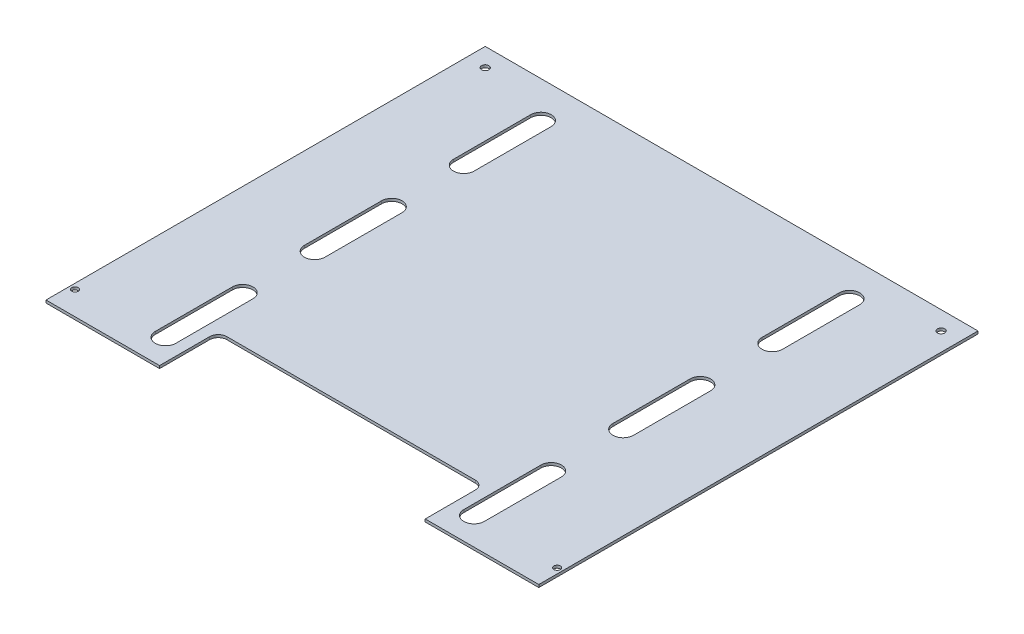
SolidWorks part; units mm, degrees
material "PC High Viscosity"
ref_plane "Front Plane" through (0, 0, 0) normal (0, 0, 1) x (1, 0, 0)
ref_plane "Top Plane" through (0, 0, 0) normal (0, 1, 0) x (1, 0, 0)
ref_plane "Right Plane" through (0, 0, 0) normal (1, 0, 0) x (0, 0, -1)
sketch "Sketch1" plane through (0, 0, 0) normal (0, 1, 0) x (1, 0, 0)
  line L1 (-146.05, 130.175) -> (146.05, 130.175)
  line L2 (-146.05, 130.175) -> (-146.05, -130.175)
  line L3 (-146.05, -130.175) -> (146.05, -130.175)
  line L4 (146.05, 130.175) -> (146.05, -130.175)
  line L5 (-146.05, 130.175) -> (146.05, -130.175) construction
  line L6 (-146.05, -130.175) -> (146.05, 130.175) construction
  line L16 (-135.128, 119.253) -> (135.128, 119.253) construction
  line L18 (-91.44, 18.923) -> (-91.44, -25.273) construction
  line L19 (91.44, 18.923) -> (91.44, -25.273) construction
  line L20 (-91.44, -3.175) -> (91.44, -3.175) construction
  line L21 (0, 127) -> (0, -88.9) construction
  circle A4 centre (-135.128, 119.253) radius 2.1527
  circle A6 centre (135.128, 119.253) radius 2.1527
  point P0 (0, 0)
  point P6 (0, 0)
  point P7 (0, 0)
  point P13 (0, -88.9)
  point P14 (0, -130.175)
  point P37 (0, 119.253)
  dimension "D9" = 4.3053
  dimension "D1" = 292.1
  dimension "D2" = 260.35
  dimension "D7" = 10.922
  dimension "D8" = 10.922
extrude "Boss-Extrude1" add sketch "Sketch1" along normal blind 1.5875 contours L1 L2 L3 L4 region at (0, 0, 0.0457)
sketch "Sketch5" plane through (0, 1.5875, 0) normal (0, 1, 0) x (1, 0, 0)
  line L0 (-91.44, 108.585) -> (-91.44, 62.865) construction
  line L1 (-85.344, 108.585) -> (-85.344, 62.865)
  line L2 (-97.536, 108.585) -> (-97.536, 62.865)
  line L3 (-146.05, 130.175) -> (-146.05, -130.175) construction
  line L4 (-146.05, 130.175) -> (146.05, 130.175) construction
  arc A0 (-85.344, 108.585) -> (-97.536, 108.585) centre (-91.44, 108.585) ccw
  arc A1 (-97.536, 62.865) -> (-85.344, 62.865) centre (-91.44, 62.865) ccw
  point P2 (-91.44, 85.725)
  dimension "D1" = 48.514
  dimension "D2" = 12.192
  dimension "D3" = 21.59
  dimension "D4" = 45.72
extrude "Cut-Extrude2" cut sketch "Sketch5" against normal through all
pattern_linear "LPattern2" count 3 spacing 88.392 along (0, 0, 1) of "Cut-Extrude2"
mirror "Mirror1" about plane through (0, 0, 0) normal (1, 0, 0) of "LPattern2", "Cut-Extrude2"
sketch "Sketch6" plane through (0, 1.5875, 0) normal (0, 1, 0) x (1, 0, 0)
  line L0 (-146.05, 130.175) -> (-146.05, -130.175) construction
  line L1 (146.05, 130.175) -> (146.05, -130.175) construction
  line L2 (-146.05, -130.175) -> (146.05, -130.175) construction
  circle A0 centre (-142.875, -116.1542) radius 1.8987
  circle A1 centre (142.875, -116.1542) radius 1.8987
  dimension "D1" = 3.7973
  dimension "D2" = 3.7973
  dimension "D3" = 3.175
  dimension "D4" = 3.175
  dimension "D5" = 14.0208
  dimension "D6" = 14.0208
extrude "Cut-Extrude3" cut sketch "Sketch6" against normal through all
sketch "Sketch7" plane through (0, 1.5875, 0) normal (0, 1, 0) x (1, 0, 0)
  line L0 (-146.05, -130.175) -> (146.05, -130.175) construction
  line L1 (-78.74, -130.175) -> (78.74, -130.175)
  line L2 (-78.74, -130.175) -> (-78.74, -95.377)
  line L3 (-78.74, -95.377) -> (78.74, -95.377)
  line L4 (78.74, -130.175) -> (78.74, -95.377)
  line L5 (-146.05, 130.175) -> (-146.05, -130.175) construction
  line L6 (146.05, 130.175) -> (146.05, -130.175) construction
  dimension "D1" = 67.31
  dimension "D2" = 67.31
  dimension "D3" = 34.798
extrude "Cut-Extrude4" cut sketch "Sketch7" against normal through all
fillet "Fillet1" radius 5.08 2 edges at (78.74, 0.7937, 95.377) (-78.74, 0.7937, 95.377)
